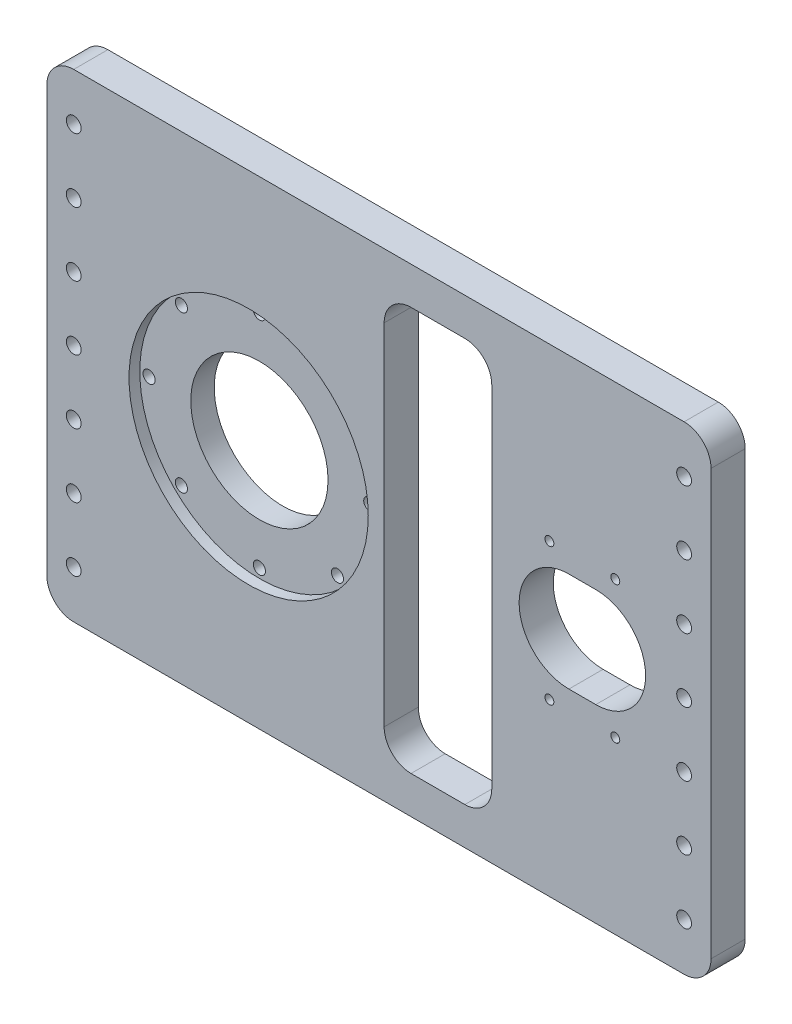
SolidWorks part; units mm, degrees
note: The reader was unsure of these and kept them because the rebuilt part matched: shared geometry of "Sketch8<3>".
material "6061-T6 (SS)"
ref_plane "Front Plane" through (0, 0, 0) normal (0, 0, 1) x (1, 0, 0)
ref_plane "Top Plane" through (0, 0, 0) normal (0, 1, 0) x (1, 0, 0)
ref_plane "Right Plane" through (0, 0, 0) normal (1, 0, 0) x (0, 0, -1)
sketch "Sketch1" plane through (0, 0, 0) normal (0, 0, 1) x (1, 0, 0)
  line L1 (-210, 95) -> (210, 95)
  line L2 (-210, 95) -> (-210, -95)
  line L3 (-210, -95) -> (210, -95)
  line L4 (210, 95) -> (210, -95)
  line L5 (-210, 95) -> (210, -95) construction
  line L6 (-210, -95) -> (210, 95) construction
  point P0 (0, 0)
  dimension "D1" = 420
  dimension "D2" = 190
extrude "Boss-Extrude1" add sketch "Sketch1" along normal blind 12.7
sketch "Sketch2" plane through (0, 0, 12.7) normal (0, 0, 1) x (1, 0, 0)
  line L0 (210, -95) -> (210, 95) construction
  line L1 (200, 85) -> (-200, 85) construction
  line L2 (200, 85) -> (200, -85) construction
  line L3 (200, -85) -> (-200, -85) construction
  line L4 (-200, 85) -> (-200, -85) construction
  line L5 (200, 85) -> (-200, -85) construction
  line L6 (200, -85) -> (-200, 85) construction
  line L7 (210, 95) -> (-210, 95) construction
  line L10 (-210, -95) -> (210, -95) construction
  line L11 (-210, 95) -> (-210, -95) construction
  line L12 (0, 85) -> (0, -85) construction
  line L13 (-200, 0) -> (200, 0) construction
  point P0 (0, 0)
  point P10 (200, -40)
  point P13 (200, 0)
  point P14 (200, 40)
  point P15 (-200, 0)
  point P16 (0, -85)
  point P17 (0, 85)
  point P18 (-150, 85)
  point P19 (-60, 85)
  point P24 (150, 85)
  point P25 (60, 85)
  point P28 (-150, -85)
  point P29 (-60, -85)
  point P30 (0, -85)
  point P31 (60, -85)
  point P32 (150, -85)
  dimension "D1" = 10
  dimension "D2" = 10
  dimension "D3" = 55
  dimension "D4" = 55
  dimension "D5" = 60
  dimension "D6" = 150
hole_wizard "M5 Clearance Hole1" [suppressed] positions "Sketch3" profile "Sketch4" hole size "M5" standard "ANSI Metric"
sketch "Sketch3" plane through (0, 0, 12.7) normal (0, 0, 1) x (1, 0, 0)
  line L0 (-200, 85) -> (-200, -85) construction
  point P0 (200, 40)
  point P3 (200, 0)
  point P6 (200, -40)
  point P9 (150, 85)
  point P12 (60, 85)
  point P15 (-60, 85)
  point P18 (-150, 85)
  point P21 (-200, 40)
  point P25 (-200, 0)
  point P28 (-200, -40)
  point P30 (-150, -85)
  point P33 (0, 85)
  point P36 (0, -85)
  point P39 (-60, -85)
  point P42 (60, -85)
  point P45 (150, -85)
sketch "Sketch4" plane through (200, 40, 12.7) normal (1, 0, 0) x (0, -1, 0)
  line L0 (0, 0) -> (0, 12.7)
  line L1 (0, 12.7) -> (2.75, 12.7)
  line L2 (2.75, 12.7) -> (2.75, 0)
  line L5 (2.75, 0) -> (0, 0)
  line L11 (0, -6.35) -> (0, 107.95) construction
  dimension "Thru Hole Dia." = 5.5
  dimension "Thru Hole Depth" = 12.7
fillet "Fillet1" radius 10 4 edges at (-210, 95, 6.35) (-210, -95, 6.35) (210, -95, 6.35) (210, 95, 6.35)
sketch "Sketch5" plane through (0, 0, 12.7) normal (0, 0, 1) x (1, 0, 0)
  circle A0 centre (0, 0) radius 62.5 construction
  point P3 (0, -62.5)
  point P7 (-36.7366, -50.5636)
  point P8 (-59.441, -19.3136)
  point P9 (-59.441, 19.3136)
  point P10 (-36.7366, 50.5636)
  point P11 (0, 62.5)
  point P12 (36.7366, 50.5636)
  point P13 (59.441, 19.3136)
  point P14 (59.441, -19.3136)
  point P15 (36.7366, -50.5636)
  dimension "D1" = 125
  dimension "D2" = 10
hole_wizard "1/4 Clearance Hole1" [suppressed] positions "Sketch6" profile "Sketch7" hole size "1/4" standard "ANSI Inch"
sketch "Sketch6" plane through (0, 0, 6.35) normal (0, 0, 1) x (1, 0, 0)
  point P0 (59.441, -19.3136)
  point P3 (36.7366, -50.5636)
  point P6 (0, -62.5)
  point P9 (-36.7366, -50.5636)
  point P12 (-59.441, -19.3136)
  point P15 (59.441, 19.3136)
  point P18 (36.7366, 50.5636)
  point P21 (0, 62.5)
  point P24 (-36.7366, 50.5636)
  point P27 (-59.441, 19.3136)
sketch "Sketch7" plane through (59.441, -19.3136, 6.35) normal (1, 0, 0) x (0, -1, 0)
  line L0 (0, 0) -> (0, 6.35)
  line L1 (0, 6.35) -> (3.3782, 6.35)
  line L2 (3.3782, 6.35) -> (3.3782, 0)
  line L5 (3.3782, 0) -> (0, 0)
  line L11 (0, -6.35) -> (0, 107.95) construction
  dimension "Thru Hole Dia." = 6.7564
  dimension "Thru Hole Depth" = 6.35
sketch "Sketch8" plane through (0, 0, 12.7) normal (0, 0, 1) x (1, 0, 0)
  line L0 (0, 95) -> (0, -95) construction
  line L1 (200, 95) -> (-200, 95) construction
  line L2 (-200, -95) -> (200, -95) construction
  line L3 (-210, 0) -> (210, 0) construction
  line L4 (-210, 85) -> (-210, -85) construction
  line L5 (210, -85) -> (210, 85) construction
  line L6 (-210, 0) -> (210, 0) construction
  circle A0 centre (0, 0) radius 25.5
  circle A1 centre (0, 0) radius 44.45
  dimension "D2" = 51
  dimension "D3" = 88.9
extrude "Cut-Extrude1" cut sketch "Sketch8" against normal blind 4 contours A1 A0
extrude "Cut-Extrude2" cut sketch "Sketch8<3>" against normal through all contours A0
sketch "Sketch8<3>" plane through (0, 0, 12.7) normal (0, 0, 1) x (1, 0, 0) same geometry as "Sketch8"
sketch "Sketch9" plane through (0, 0, 0) normal (0, 0, -1) x (-1, 0, 0)
  circle A0 centre (0, 0) radius 41 construction
  point P3 (0, 41)
  point P7 (28.9914, 28.9914)
  point P8 (41, 0)
  point P9 (28.9914, -28.9914)
  point P10 (0, -41)
  point P11 (-28.9914, -28.9914)
  point P12 (-41, 0)
  point P13 (-28.9914, 28.9914)
  dimension "D1" = 82
  dimension "D2" = 8
hole_wizard "CBORE for #8 Binding Head Machine Screw1" positions "Sketch10" profile "Sketch11" counterbore size "#8" standard "ANSI Inch"
sketch "Sketch10" plane through (0, 0, 0) normal (0, 0, -1) x (-1, 0, 0)
  point P0 (0, 41)
  point P3 (0, -41)
  point P6 (28.9914, -28.9914)
  point P9 (-28.9914, -28.9914)
  point P12 (-41, 0)
  point P15 (41, 0)
  point P18 (-28.9914, 28.9914)
  point P21 (28.9914, 28.9914)
sketch "Sketch11" plane through (0, 41, 0) normal (1, 0, 0) x (0, 1, 0)
  line L0 (0, 0) -> (0, 11.3519)
  line L1 (0, 11.3519) -> (2.25, 10)
  line L2 (2.25, 10) -> (2.25, 4)
  line L3 (2.25, 4) -> (4.125, 4)
  line L4 (4.125, 4) -> (4.125, 0)
  line L5 (4.125, 0) -> (0, 0)
  line L10 (0, 11.3519) -> (-2.25, 10) construction
  line L11 (0, -6.35) -> (0, 107.95) construction
  dimension "Hole Dia." = 4.5
  dimension "Hole Depth" = 10
  dimension "C'Bore Dia." = 8.25
  dimension "C'Bore Depth" = 4
  dimension "Drill Angle" = 118
sketch "Sketch12" plane through (0, 0, 12.7) normal (0, 0, 1) x (1, 0, 0)
  line L0 (0, 0) -> (124, 0) construction
  line L1 (119, -18.5) -> (129, -18.5)
  line L2 (129, 18.5) -> (119, 18.5)
  line L3 (124, 18.5) -> (124, -18.5) construction
  arc A0 (129, -18.5) -> (129, 18.5) centre (129, 0) ccw
  arc A1 (119, 18.5) -> (119, -18.5) centre (119, 0) ccw
  point P12 (124, 0)
  dimension "D1" = 124
extrude "Cut-Extrude3" cut sketch "Sketch12" against normal through all
sketch "Sketch13" plane through (0, 0, 12.7) normal (0, 0, 1) x (1, 0, 0)
  line L0 (124, 18.5) -> (124, -18.5) construction
  line L1 (129, 18.5) -> (119, 18.5) construction
  line L2 (119, -18.5) -> (129, -18.5) construction
  line L4 (111.75, 25.5) -> (136.25, 25.5) construction
  line L5 (111.75, 25.5) -> (111.75, -25.5) construction
  line L6 (111.75, -25.5) -> (136.25, -25.5) construction
  line L7 (136.25, 25.5) -> (136.25, -25.5) construction
  line L8 (111.75, 25.5) -> (136.25, -25.5) construction
  line L9 (111.75, -25.5) -> (136.25, 25.5) construction
  point P6 (124, 0)
  dimension "D1" = 51
  dimension "D2" = 24.5
hole_wizard "Tap Drill for M4x0.7 Tap1" positions "Sketch14" profile "Sketch15" hole size "M4x0.7" standard "ANSI Metric" end condition through all
sketch "Sketch14" plane through (0, 0, 12.7) normal (0, 0, 1) x (1, 0, 0)
  point P0 (111.75, 25.5)
  point P3 (136.25, 25.5)
  point P6 (111.75, -25.5)
  point P9 (136.25, -25.5)
sketch "Sketch15" plane through (111.75, 25.5, 12.7) normal (1, 0, 0) x (0, -1, 0)
  line L0 (0, 0) -> (0, 12.7)
  line L1 (0, 12.7) -> (1.65, 12.7)
  line L2 (1.65, 12.7) -> (1.65, 0)
  line L5 (1.65, 0) -> (0, 0)
  line L11 (0, -6.35) -> (0, 107.95) construction
  dimension "Thru Hole Dia." = 3.3
  dimension "Thru Hole Depth" = 12.7
sketch "Sketch18" plane through (0, 0, 12.7) normal (0, 0, 1) x (1, 0, 0)
  line L0 (-75, 95) -> (-75, -95)
  line L1 (200, 95) -> (-200, 95) construction
  line L2 (-200, -95) -> (200, -95) construction
  line L3 (210, -85) -> (210, 85) construction
  line L4 (-75, 95) -> (-210, 95)
  line L5 (-210, 95) -> (-210, -95)
  line L6 (-210, -95) -> (-75, -95)
  dimension "D1" = 285
extrude "Cut-Extrude4" cut sketch "Sketch18" against normal through all
fillet "Fillet2" radius 10 2 edges at (-75, 95, 6.35) (-75, -95, 6.35)
sketch "Sketch19" [suppressed] plane through (0, 0, 12.7) normal (0, 0, 1) x (1, 0, 0)
  circle A0 centre (150, -85) radius 7.911
  circle A1 centre (200, -40) radius 5.1523
sketch "Sketch20" plane through (0, 0, 12.7) normal (0, 0, 1) x (1, 0, 0)
  line L0 (-65, -95) -> (-65, 95) construction
  line L1 (-65, -95) -> (200, -95) construction
  line L2 (200, 95) -> (-65, 95) construction
  line L3 (-75, -85) -> (-75, 85) construction
  line L4 (-65, 0) -> (-121.0167, 0) construction
  point P8 (-65, 0)
  point P9 (-65, -31.6667)
  point P10 (-65, -63.3333)
  point P14 (-65, 31.6667)
  point P15 (-65, 63.3333)
  dimension "D1" = 10
  dimension "D2" = 31.6667
  dimension "D3" = 31.6667
hole_wizard "M5 Clearance Hole2" [suppressed] positions "Sketch23" profile "Sketch24" hole size "M5" standard "ANSI Metric"
sketch "Sketch23" plane through (0, 0, 12.7) normal (0, 0, 1) x (1, 0, 0)
  point P0 (-65, -63.3333)
  point P3 (-65, -31.6667)
  point P6 (-65, 0)
  point P9 (-65, 31.6667)
  point P12 (-65, 63.3333)
sketch "Sketch24" plane through (-65, -63.3333, 12.7) normal (1, 0, 0) x (0, -1, 0)
  line L0 (0, 0) -> (0, 12.7)
  line L1 (0, 12.7) -> (2.75, 12.7)
  line L2 (2.75, 12.7) -> (2.75, 0)
  line L5 (2.75, 0) -> (0, 0)
  line L11 (0, -6.35) -> (0, 107.95) construction
  dimension "Thru Hole Dia." = 5.5
  dimension "Thru Hole Depth" = 12.7
sketch "Sketch25" plane through (0, 0, 12.7) normal (0, 0, 1) x (1, 0, 0)
  line L0 (260.2972, -75) -> (-119.7232, -75) construction
  line L1 (260.2972, 75) -> (-119.7232, 75) construction
  line L2 (210, -85) -> (210, 85) construction
  line L3 (210, -75) -> (171.8095, -75)
  line L4 (171.8095, -75) -> (171.8095, 75)
  line L5 (171.8095, 75) -> (210, 75)
  line L6 (210, -75) -> (210, 75)
extrude "Cut-Extrude5" cut sketch "Sketch25" against normal through all
fillet "Fillet3" [suppressed] radius 10
sketch "Sketch26" plane through (0, 0, 12.7) normal (0, 0, 1) x (1, 0, 0)
  line L0 (100.5, 0) -> (0, 0) construction
  line L1 (210, 75) -> (171.8095, 75) construction
  line L2 (50.3403, -75) -> (90.3403, -75)
  line L3 (50.3403, -75) -> (50.3403, 75)
  line L4 (50.3403, 75) -> (90.3403, 75)
  line L5 (90.3403, -75) -> (90.3403, 75)
  line L6 (50.3403, -75) -> (90.3403, 75) construction
  line L7 (50.3403, 75) -> (90.3403, -75) construction
  arc A0 (119, 18.5) -> (119, -18.5) centre (119, 0) ccw construction
  point P6 (70.3403, 0)
  dimension "D1" = 40
extrude "Cut-Extrude6" cut sketch "Sketch26" against normal through all
fillet "Fillet4" radius 10 4 edges at (90.3403, 75, 6.35) (50.3403, 75, 6.35) (90.3403, -75, 6.35) (50.3403, -75, 6.35)
sketch "Sketch27" plane through (0, 0, 12.7) normal (0, 0, 1) x (1, 0, 0)
  line L0 (-75, -75) -> (-55, -75)
  line L1 (-55, -75) -> (-55, 75)
  line L2 (-55, 75) -> (-75, 75)
  line L3 (-75, 75) -> (-75, -75)
  line L4 (-75, -85) -> (-75, 85) construction
  line L5 (260.2972, -75) -> (-119.7232, -75) construction
  line L6 (260.2972, 75) -> (-119.7232, 75) construction
  dimension "D1" = 20
extrude "Cut-Extrude7" [suppressed] cut sketch "Sketch27" against normal through all
fillet "Fillet5" [suppressed] radius 10
sketch "Sketch28" [suppressed] plane through (0, 0, 12.7) normal (0, 0, 1) x (1, 0, 0)
  line L0 (210, -85) -> (-75, -85) construction
  line L1 (67.5, 85) -> (67.5, 115.0441) construction
  line L2 (210, 85) -> (-75, 85) construction
  line L3 (171.8095, 0) -> (117.0649, 0) construction
  line L4 (171.8095, 65) -> (171.8095, -65) construction
  point P4 (67.5, -85)
  point P5 (67.5, 85)
  point P10 (31.875, 85)
  point P11 (-3.75, 85)
  point P12 (-39.375, 85)
  point P20 (174.375, 85)
  point P21 (138.75, 85)
  point P22 (103.125, 85)
  point P23 (103.125, -85)
  point P24 (138.75, -85)
  point P25 (174.375, -85)
  point P26 (-39.375, -85)
  point P27 (-3.75, -85)
  point P28 (31.875, -85)
  dimension "D1" = 35.625
  dimension "D2" = 35.625
  dimension "D3" = 35.625
hole_wizard "M5 Clearance Hole3" [suppressed] positions "Sketch33" profile "Sketch34" hole size "M5" standard "ANSI Metric"
sketch "Sketch33" [suppressed] plane through (0, 0, 12.7) normal (0, 0, 1) x (1, 0, 0)
  point P0 (174.375, -85)
  point P3 (138.75, -85)
  point P6 (103.125, -85)
  point P9 (67.5, -85)
  point P12 (31.875, -85)
  point P15 (-3.75, -85)
  point P18 (-39.375, -85)
  point P21 (174.375, 85)
  point P24 (138.75, 85)
  point P27 (103.125, 85)
  point P30 (67.5, 85)
  point P33 (31.875, 85)
  point P36 (-3.75, 85)
  point P39 (-39.375, 85)
sketch "Sketch34" plane through (174.375, -85, 12.7) normal (1, 0, 0) x (0, -1, 0)
  line L0 (0, 0) -> (0, 12.7)
  line L1 (0, 12.7) -> (2.75, 12.7)
  line L2 (2.75, 12.7) -> (2.75, 0)
  line L5 (2.75, 0) -> (0, 0)
  line L11 (0, -6.35) -> (0, 107.95) construction
  dimension "Thru Hole Dia." = 5.5
  dimension "Thru Hole Depth" = 12.7
sketch "Sketch35" plane through (0, 0, 12.7) normal (0, 0, 1) x (1, 0, 0)
  line L0 (171.8095, -75) -> (171.8095, -95)
  line L1 (-65, -95) -> (200, -95) construction
  line L2 (171.8095, -95) -> (219.3865, -95)
  line L3 (219.3865, -95) -> (219.3865, 95)
  line L4 (219.3865, 95) -> (171.8095, 95)
  line L5 (200, 95) -> (-65, 95) construction
  line L6 (171.8095, 95) -> (171.8095, -75)
extrude "Cut-Extrude8" cut sketch "Sketch35" against normal through all both and the other way through all
fillet "Fillet6" radius 10 2 edges at (171.8095, 95, 6.35) (171.8095, -95, 6.35)
sketch "Sketch36" plane through (0, 0, 12.7) normal (0, 0, 1) x (1, 0, 0)
  line L0 (161.8095, -95) -> (161.8095, 95) construction
  line L1 (171.8095, 85) -> (171.8095, -85) construction
  line L2 (-65, -95) -> (161.8095, -95) construction
  line L3 (161.8095, 95) -> (-65, 95) construction
  line L4 (171.8095, 0) -> (230.2884, 0) construction
  line L5 (48.4048, -95) -> (48.4048, 95) construction
  line L6 (-75, 0) -> (-133.4789, 0) construction
  line L7 (-65, -95) -> (-65, 95) construction
  point P4 (161.8095, -23.75)
  point P7 (161.8095, -47.5)
  point P10 (161.8095, 0)
  point P11 (161.8095, -71.25)
  point P15 (161.8095, 23.75)
  point P16 (161.8095, 47.5)
  point P17 (161.8095, 71.25)
  point P24 (-65, 71.25)
  point P25 (-65, 47.5)
  point P26 (-65, 23.75)
  point P27 (-65, -71.25)
  point P28 (-65, 0)
  point P29 (-65, -47.5)
  point P30 (-65, -23.75)
  dimension "D1" = 10
  dimension "D2" = 23.75
  dimension "D3" = 23.75
  dimension "D4" = 23.75
hole_wizard "M5 Clearance Hole4" positions "Sketch37" profile "Sketch38" hole size "M5" standard "ANSI Metric" end condition through all
sketch "Sketch37" plane through (0, 0, 12.7) normal (0, 0, 1) x (1, 0, 0)
  point P0 (161.8095, -71.25)
  point P3 (161.8095, -47.5)
  point P6 (161.8095, -23.75)
  point P9 (161.8095, 0)
  point P12 (161.8095, 23.75)
  point P15 (161.8095, 47.5)
  point P18 (161.8095, 71.25)
  point P21 (-65, 71.25)
  point P24 (-65, 47.5)
  point P27 (-65, 23.75)
  point P30 (-65, 0)
  point P33 (-65, -23.75)
  point P36 (-65, -47.5)
  point P39 (-65, -71.25)
sketch "Sketch38" plane through (161.8095, -71.25, 12.7) normal (1, 0, 0) x (0, -1, 0)
  line L0 (0, 0) -> (0, 12.7)
  line L1 (0, 12.7) -> (2.75, 12.7)
  line L2 (2.75, 12.7) -> (2.75, 0)
  line L5 (2.75, 0) -> (0, 0)
  line L11 (0, -6.35) -> (0, 107.95) construction
  dimension "Thru Hole Dia." = 5.5
  dimension "Thru Hole Depth" = 12.7
sketch "Sketch39" plane through (0, 0, 12.7) normal (0, 0, 1) x (1, 0, 0)
  line L0 (161.8095, -71.25) -> (161.8095, -47.5) construction
  line L1 (161.8095, -59.375) -> (145.4485, -59.375) construction
  line L2 (161.8095, -47.5) -> (161.8095, -23.75) construction
  line L3 (161.8095, -23.75) -> (161.8095, 0) construction
  line L4 (161.8095, 0) -> (161.8095, 23.75) construction
  line L5 (161.8095, 23.75) -> (161.8095, 47.5) construction
  line L6 (161.8095, 47.5) -> (161.8095, 71.25) construction
  line L7 (161.8095, 59.375) -> (140.0285, 59.375) construction
  line L8 (161.8095, 35.625) -> (140.0285, 35.625) construction
  line L9 (161.8095, 11.875) -> (141.2541, 11.875) construction
  line L10 (161.8095, -11.875) -> (148.4561, -11.875) construction
  line L11 (161.8095, -35.625) -> (145.4485, -35.625) construction
  line L12 (161.8095, 0) -> (181.3967, 0) construction
  line L13 (161.8095, 47.5) -> (161.8095, 23.75) construction
  line L14 (161.8095, 71.25) -> (161.8095, 47.5) construction
  line L15 (48.4048, -95) -> (48.4048, -133.2666) construction
  line L16 (-65, -95) -> (161.8095, -95) construction
  line L17 (-65, 71.25) -> (-65, 47.5) construction
  line L18 (-65, 47.5) -> (-65, 23.75) construction
  line L19 (-65, 0) -> (-84.5872, 0) construction
  line L20 (-65, -35.625) -> (-48.639, -35.625) construction
  line L21 (-65, -11.875) -> (-51.6466, -11.875) construction
  line L22 (-65, 11.875) -> (-44.4445, 11.875) construction
  line L23 (-65, 35.625) -> (-43.2189, 35.625) construction
  line L24 (-65, 59.375) -> (-43.2189, 59.375) construction
  line L25 (-65, 47.5) -> (-65, 71.25) construction
  line L26 (-65, 23.75) -> (-65, 47.5) construction
  line L27 (-65, 0) -> (-65, 23.75) construction
  line L28 (-65, -23.75) -> (-65, 0) construction
  line L29 (-65, -47.5) -> (-65, -23.75) construction
  line L30 (-65, -59.375) -> (-48.639, -59.375) construction
  line L31 (-65, -71.25) -> (-65, -47.5) construction
  circle A0 centre (161.8095, -71.25) radius 2.75
  circle A1 centre (161.8095, -71.25) radius 1
  circle A2 centre (161.8095, -47.5) radius 1
  circle A3 centre (161.8095, -47.5) radius 2.75
  circle A4 centre (161.8095, -23.75) radius 2.75
  circle A5 centre (161.8095, -23.75) radius 1
  circle A6 centre (161.8095, 0) radius 1
  circle A7 centre (161.8095, 0) radius 2.75
  circle A8 centre (161.8095, 23.75) radius 1
  circle A9 centre (161.8095, 23.75) radius 2.75
  circle A10 centre (161.8095, 47.5) radius 2.75
  circle A11 centre (161.8095, 47.5) radius 1
  circle A12 centre (161.8095, 71.25) radius 1
  circle A13 centre (161.8095, 71.25) radius 2.75
  circle A14 centre (-65, 71.25) radius 2.75
  circle A15 centre (-65, 71.25) radius 1
  circle A16 centre (-65, 47.5) radius 1
  circle A17 centre (-65, 47.5) radius 2.75
  circle A18 centre (-65, 23.75) radius 2.75
  circle A19 centre (-65, 23.75) radius 1
  circle A20 centre (-65, 0) radius 2.75
  circle A21 centre (-65, 0) radius 1
  circle A22 centre (-65, -23.75) radius 1
  circle A23 centre (-65, -23.75) radius 2.75
  circle A24 centre (-65, -47.5) radius 2.75
  circle A25 centre (-65, -47.5) radius 1
  circle A26 centre (-65, -71.25) radius 1
  circle A27 centre (-65, -71.25) radius 2.75
  dimension "D1" = 2
extrude "Boss-Extrude2" [suppressed] add sketch "Sketch39" against normal up to surface (12.7 mm away)
sketch "Sketch40" plane through (0, 0, 8.7) normal (0, 0, 1) x (1, 0, 0)
  circle A0 centre (0, 0) radius 22.325
  circle A1 centre (0, 0) radius 25.5
  dimension "D1" = 44.65
extrude "Boss-Extrude3" [suppressed] add sketch "Sketch40" against normal up to surface (8.7 mm away)
sketch "Sketch41" plane through (0, 0, 0) normal (0, 0, -1) x (-1, 0, 0)
  line L0 (75, 85) -> (75, 95)
  line L1 (75, 95) -> (65, 95)
  line L2 (-161.8095, 95) -> (65, 95) construction
  line L3 (75, 0) -> (111.3727, 0) construction
  line L4 (75, -85) -> (75, 85) construction
  line L5 (-48.4048, 95) -> (-48.4048, 116.3875) construction
  line L6 (75, -95) -> (65, -95)
  line L7 (75, -85) -> (75, -95)
  line L8 (-171.8095, -85) -> (-171.8095, -95)
  line L9 (-171.8095, -95) -> (-161.8095, -95)
  line L10 (-171.8095, 95) -> (-161.8095, 95)
  line L11 (-171.8095, 85) -> (-171.8095, 95)
  arc A0 (75, 85) -> (65, 95) centre (65, 85) ccw construction
  arc A1 (75, 85) -> (65, 95) centre (65, 85) ccw
  arc A2 (75, -85) -> (65, -95) centre (65, -85) cw
  arc A3 (-171.8095, -85) -> (-161.8095, -95) centre (-161.8095, -85) ccw
  arc A4 (-171.8095, 85) -> (-161.8095, 95) centre (-161.8095, 85) cw
extrude "Boss-Extrude4" add sketch "Sketch41" against normal up to surface (12.7 mm away) up to face at (164.5595, -71.25, 12.7)
sketch "Sketch42" plane through (0, 0, 0) normal (0, 0, -1) x (-1, 0, 0)
  line L0 (-171.8095, 95) -> (-171.8095, -95) construction
  line L1 (75, 95) -> (-171.8095, 95)
  line L2 (75, 95) -> (75, 88.904)
  line L3 (75, 88.904) -> (-171.8095, 88.904)
  line L4 (-171.8095, 95) -> (-171.8095, 88.904)
  line L5 (-171.8095, 0) -> (-226.5613, 0) construction
  line L6 (-171.8095, -95) -> (-171.8095, -88.904)
  line L7 (75, -88.904) -> (-171.8095, -88.904)
  line L8 (75, -95) -> (75, -88.904)
  line L9 (75, -95) -> (-171.8095, -95)
  dimension "D1" = 6.096
extrude "Cut-Extrude9" cut sketch "Sketch42" against normal up to surface (12.7 mm away) up to face at (164.5595, -71.25, 12.7)
fillet "Fillet7" radius 10 4 edges at (-75, -88.904, 6.35) (171.8095, -88.904, 6.35) (171.8095, 88.904, 6.35) (-75, 88.904, 6.35)
